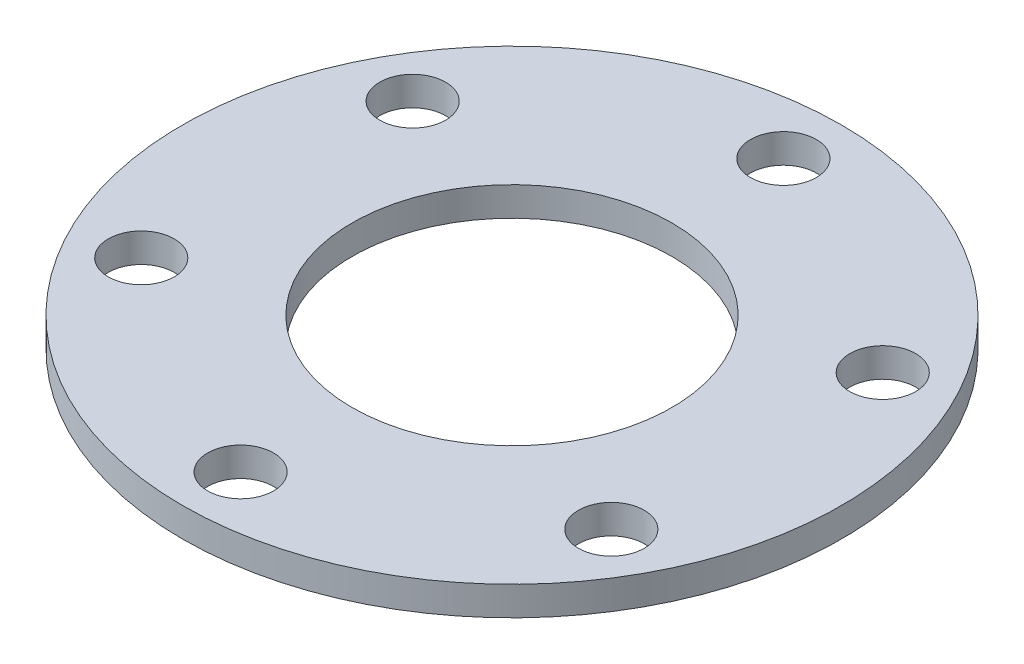
SolidWorks part; units mm, degrees
ref_plane "Front Plane" through (0, 0, 0) normal (0, 0, 1) x (1, 0, 0)
ref_plane "Top Plane" through (0, 0, 0) normal (0, 1, 0) x (1, 0, 0)
ref_plane "Right Plane" through (0, 0, 0) normal (1, 0, 0) x (0, 0, -1)
sketch "Sketch1" plane through (0, 0, 0) normal (0, 1, 0) x (1, 0, 0)
  circle A0 centre (0, 0) radius 17
  circle A1 centre (0, 0) radius 8.25
  circle A2 centre (0, 0) radius 14 construction
  circle A3 centre (0, 14) radius 1.7
  circle A6 centre (0, 0) radius 12 construction
  circle A7 centre (12.1244, 7) radius 1.7
  circle A8 centre (12.1244, -7) radius 1.7
  circle A9 centre (0, -14) radius 1.7
  circle A10 centre (-12.1244, -7) radius 1.7
  circle A11 centre (-12.1244, 7) radius 1.7
  point P13 (0, 0)
  point P21 (0, 0)
  dimension "D1" = 34
  dimension "D2" = 16.5
  dimension "D3" = 28
  dimension "D4" = 3.4
  dimension "D6" = 24
  dimension "D5" = 6
extrude "Boss-Extrude1" add sketch "Sketch1" along normal blind 1.5
